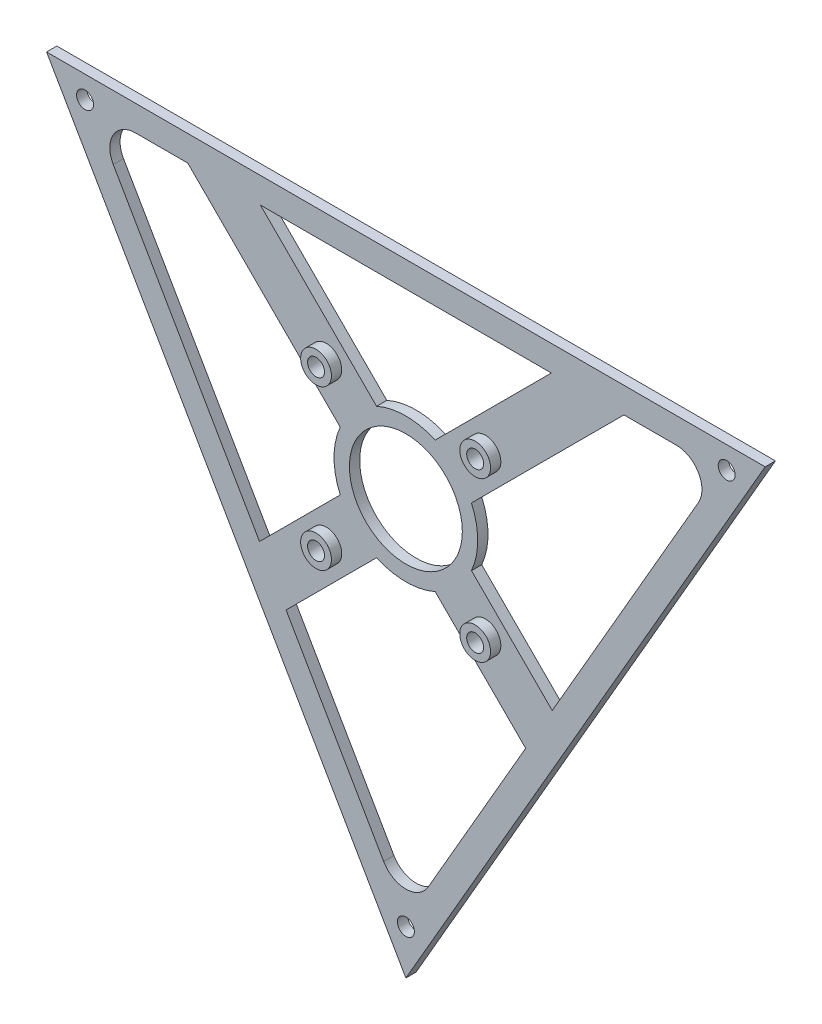
SolidWorks part; units mm, degrees
material "ABS"
ref_plane "Front Plane" through (0, 0, 0) normal (0, 0, 1) x (1, 0, 0)
ref_plane "Top Plane" through (0, 0, 0) normal (0, 1, 0) x (1, 0, 0)
ref_plane "Right Plane" through (0, 0, 0) normal (1, 0, 0) x (0, 0, -1)
sketch "Sketch1" plane through (0, 0, 0) normal (0, 0, 1) x (1, 0, 0)
  line L0 (-15.5, 15.5) -> (15.5, 15.5) construction
  line L5 (0, -80.829) -> (70, 40.4145)
  line L6 (70, 40.4145) -> (-70, 40.4145)
  line L7 (-70, 40.4145) -> (0, -80.829)
  line L8 (15.5, 15.5) -> (15.5, -15.5) construction
  line L9 (15.5, -15.5) -> (-15.5, -15.5) construction
  line L10 (-15.5, -15.5) -> (-15.5, 15.5) construction
  circle A0 centre (0, 0) radius 11
  circle A1 centre (0, 0) radius 40.4145 construction
  circle A2 centre (-15.5, 15.5) radius 1.65
  circle A3 centre (0, 0) radius 11
  circle A4 centre (15.5, 15.5) radius 1.65
  circle A5 centre (0, 0) radius 11
  circle A6 centre (15.5, -15.5) radius 1.65
  circle A7 centre (0, 0) radius 11
  circle A8 centre (-15.5, -15.5) radius 1.65
  point P21 (0, 0)
  dimension "D1" = 22
  dimension "D4" = 3.3
  dimension "D2" = 15.5
  dimension "D3" = 15.5
  dimension "D6" = 140
  dimension "D5" = 4
extrude "Boss-Extrude1" add sketch "Sketch1" along normal blind 2 contours L6 L7 L5 A8 A6 A4 A2 A0 region at (-33.3961, -19.2812, 0)
shell "Shell2" thickness 1 removed face at (-13.85, -15.5, 2)
sketch "Sketch3" plane through (0, 0, 1) normal (0, 0, 1) x (1, 0, 0)
  line L0 (61.3397, 35.4145) -> (-61.3397, 35.4145)
  line L1 (-61.3397, 35.4145) -> (0, -70.829)
  line L2 (0, -70.829) -> (61.3397, 35.4145)
  line L3 (68.2679, 39.4145) -> (-68.2679, 39.4145)
  line L4 (-68.2679, 39.4145) -> (0, -78.829)
  line L5 (0, -78.829) -> (68.2679, 39.4145)
  line L6 (68.2679, 39.4145) -> (-68.2679, 39.4145)
  line L7 (-68.2679, 39.4145) -> (0, -78.829)
  line L8 (0, -78.829) -> (68.2679, 39.4145)
  circle A0 centre (0, 0) radius 12 construction
  circle A1 centre (0, 0) radius 12
  circle A2 centre (-15.5, -15.5) radius 2.65 construction
  circle A3 centre (15.5, -15.5) radius 2.65 construction
  circle A4 centre (15.5, 15.5) radius 2.65 construction
  circle A5 centre (-15.5, 15.5) radius 2.65 construction
  circle A6 centre (-15.5, -15.5) radius 2.65
  circle A7 centre (15.5, -15.5) radius 2.65
  circle A8 centre (15.5, 15.5) radius 2.65
  circle A9 centre (-15.5, 15.5) radius 2.65
  circle A10 centre (-15.5, 15.5) radius 4.65
  circle A11 centre (15.5, 15.5) radius 4.65
  circle A12 centre (0, 0) radius 14
  circle A13 centre (15.5, -15.5) radius 4.65
  circle A14 centre (-15.5, -15.5) radius 4.65
  circle M8 centre (-15.5, -15.5) radius 2.65
  circle M9 centre (15.5, -15.5) radius 2.65
  circle M10 centre (15.5, 15.5) radius 2.65
  circle M11 centre (-15.5, 15.5) radius 2.65
  circle M12 centre (0, 0) radius 12
  line M13 (68.2679, 39.4145) -> (-68.2679, 39.4145)
  line M14 (-68.2679, 39.4145) -> (0, -78.829)
  line M15 (0, -78.829) -> (68.2679, 39.4145)
  dimension "D1" = 0
  dimension "D2" = 4
  dimension "D3" = 2
extrude "Boss-Extrude2" add sketch "Sketch3" along normal up to surface (1 mm away) contours A10 M11 | A11 M10 | A13 M9 | A14 M8 | A12 M12 | L2 L1 L0 M15 M13 M14 region at (32.5698, -18.8042, 1) region at (-20.0185, 15.5, 1) region at (10.9815, 15.5, 1) region at (-13.604, 0, 1) region at (10.9815, -15.5, 1) region at (-20.0185, -15.5, 1) up to face at (-13.85, -15.5, 2)
sketch "Sketch4" plane through (0, 0, 1) normal (0, 0, 1) x (1, 0, 0)
  line L0 (0, 0) -> (25.9252, -25.9252) construction
  line L1 (0, -70.829) -> (61.3397, 35.4145) construction
  line L2 (5.7111, -12.7822) -> (23.337, -30.4081)
  line L3 (28.5134, -21.4423) -> (12.7822, -5.7111)
  line L4 (0, -70.829) -> (61.3397, 35.4145) construction
  line L5 (23.337, -30.4081) -> (28.5134, -21.4423)
  line L6 (0, 0) -> (0, -70.829) construction
  line L7 (-5.7111, -12.7822) -> (-23.337, -30.4081)
  line L8 (-28.5134, -21.4423) -> (-12.7822, -5.7111)
  line L9 (-23.337, -30.4081) -> (-28.5134, -21.4423)
  line L10 (0, 0) -> (-25.9252, -25.9252) construction
  line L11 (0, 0) -> (15.5, 15.5) construction
  line L12 (0, 0) -> (0, 35.4145) construction
  line L13 (61.3397, 35.4145) -> (-61.3397, 35.4145) construction
  line L14 (28.3435, 35.4145) -> (5.7111, 12.7822)
  line L15 (-15.5, 15.5) -> (0, 0) construction
  line L16 (61.3397, 35.4145) -> (-61.3397, 35.4145) construction
  line L17 (42.4856, 35.4145) -> (12.7822, 5.7111)
  line L18 (42.4856, 35.4145) -> (28.3435, 35.4145)
  line L19 (-42.4856, 35.4145) -> (-12.7822, 5.7111)
  line L20 (-28.3435, 35.4145) -> (-5.7111, 12.7822)
  line L21 (-42.4856, 35.4145) -> (-28.3435, 35.4145)
  circle A1 centre (0, 0) radius 14 construction
  circle A2 centre (0, 0) radius 14 construction
  arc A3 (5.7111, -12.7822) -> (12.7822, -5.7111) centre (0, 0) ccw
  circle A4 centre (15.5, -15.5) radius 4.65 construction
  circle A5 centre (15.5, -15.5) radius 4.65
  circle A6 centre (-15.5, -15.5) radius 4.65
  arc A7 (-5.7111, -12.7822) -> (-12.7822, -5.7111) centre (0, 0) cw
  arc A8 (-12.7822, -5.7111) -> (-5.7111, -12.7822) centre (0, 0) ccw
  arc A9 (0, -14) -> (12.7822, -5.7111) centre (0, 0) ccw
  arc A10 (12.7822, 5.7111) -> (5.7111, 12.7822) centre (0, 0) ccw
  circle A11 centre (15.5, 15.5) radius 4.65 construction
  circle A12 centre (15.5, 15.5) radius 4.65
  circle A13 centre (-15.5, 15.5) radius 4.65
  arc A14 (-12.7822, 5.7111) -> (-5.7111, 12.7822) centre (0, 0) cw
  point P7 (15.5, -15.5)
  line M18 (0, -70.829) -> (61.3397, 35.4145)
  line M19 (61.3397, 35.4145) -> (-61.3397, 35.4145)
  line M20 (-61.3397, 35.4145) -> (0, -70.829)
  circle M21 centre (0, 0) radius 14
  circle M22 centre (-15.5, -15.5) radius 4.65
  circle M23 centre (15.5, -15.5) radius 4.65
  circle M24 centre (15.5, 15.5) radius 4.65
  circle M25 centre (-15.5, 15.5) radius 4.65
  dimension "D3" = 5
  dimension "D1" = 5
  dimension "D2" = 5
  dimension "D4" = 5
extrude "Boss-Extrude3" add sketch "Sketch4" along direction (0, 0, 1) on the side of the normal blind 1 contours L8 L7 M20 M21 M22 | L3 L2 M18 M21 M23 | L17 L14 M19 M21 M24 | L20 L19 M19 M21 M25 region at (10.1372, -10.1372, 1) region at (-14.7617, -21.3574, 1) region at (24.4656, 24.0674, 1) region at (-24.4656, 24.0674, 1)
sketch "Sketch6" plane through (0, 0, 1) normal (0, 0, 1) x (1, 0, 0)
  line L0 (-12.7822, 5.7111) -> (-42.4856, 35.4145) construction
  line L1 (-42.4856, 35.4145) -> (-61.3397, 35.4145) construction
  line L2 (-61.3397, 35.4145) -> (-28.5134, -21.4423) construction
  line L3 (-28.5134, -21.4423) -> (-12.7822, -5.7111) construction
  line L4 (0, -70.829) -> (23.337, -30.4081) construction
  line L5 (23.337, -30.4081) -> (5.7111, -12.7822) construction
  line L6 (-5.7111, -12.7822) -> (-23.337, -30.4081) construction
  line L7 (-23.337, -30.4081) -> (0, -70.829) construction
  line L8 (42.4856, 35.4145) -> (12.7822, 5.7111) construction
  line L9 (12.7822, -5.7111) -> (28.5134, -21.4423) construction
  line L10 (28.5134, -21.4423) -> (61.3397, 35.4145) construction
  line L11 (61.3397, 35.4145) -> (42.4856, 35.4145) construction
  line L12 (-28.3435, 35.4145) -> (-5.7111, 12.7822) construction
  line L13 (5.7111, 12.7822) -> (28.3435, 35.4145) construction
  line L14 (28.3435, 35.4145) -> (-28.3435, 35.4145) construction
  line L15 (-12.7822, 5.7111) -> (-42.4856, 35.4145)
  line L16 (-42.4856, 35.4145) -> (-61.3397, 35.4145)
  line L17 (-61.3397, 35.4145) -> (-28.5134, -21.4423)
  line L18 (-28.5134, -21.4423) -> (-12.7822, -5.7111)
  line L19 (0, -70.829) -> (23.337, -30.4081)
  line L20 (23.337, -30.4081) -> (5.7111, -12.7822)
  line L21 (-5.7111, -12.7822) -> (-23.337, -30.4081)
  line L22 (-23.337, -30.4081) -> (0, -70.829)
  line L23 (42.4856, 35.4145) -> (12.7822, 5.7111)
  line L24 (12.7822, -5.7111) -> (28.5134, -21.4423)
  line L25 (28.5134, -21.4423) -> (61.3397, 35.4145)
  line L26 (61.3397, 35.4145) -> (42.4856, 35.4145)
  line L27 (-28.3435, 35.4145) -> (-5.7111, 12.7822)
  line L28 (5.7111, 12.7822) -> (28.3435, 35.4145)
  line L29 (28.3435, 35.4145) -> (-28.3435, 35.4145)
  arc A0 (-12.7822, 5.7111) -> (-12.7822, -5.7111) centre (0, 0) ccw construction
  arc A1 (-5.7111, -12.7822) -> (5.7111, -12.7822) centre (0, 0) ccw construction
  arc A2 (12.7822, -5.7111) -> (12.7822, 5.7111) centre (0, 0) ccw construction
  arc A3 (5.7111, 12.7822) -> (-5.7111, 12.7822) centre (0, 0) ccw construction
  arc A4 (-12.7822, 5.7111) -> (-12.7822, -5.7111) centre (0, 0) ccw
  arc A5 (-5.7111, -12.7822) -> (5.7111, -12.7822) centre (0, 0) ccw
  arc A6 (12.7822, -5.7111) -> (12.7822, 5.7111) centre (0, 0) ccw
  arc A7 (5.7111, 12.7822) -> (-5.7111, 12.7822) centre (0, 0) ccw
extrude "Cut-Extrude2" cut sketch "Sketch6" against normal through all both and the other way through all
fillet "Fillet2" radius 5 3 edges at (0, -70.829, 1) (61.3397, 35.4145, 1) (-61.3397, 35.4145, 1)
sketch "Sketch7" plane through (0, 0, 2) normal (0, 0, 1) x (1, 0, 0)
  line L1 (62.5, 36.0844) -> (-62.5, 36.0844) construction
  line L2 (-62.5, 36.0844) -> (0, -72.1688) construction
  line L3 (0, -72.1688) -> (62.5, 36.0844) construction
  circle A0 centre (-62.5, 36.0844) radius 1.65
  circle A1 centre (62.5, 36.0844) radius 1.65
  circle A2 centre (0, -72.1688) radius 1.65
  circle A3 centre (0, 0) radius 36.0844 construction
  dimension "D1" = 3.3
  dimension "D2" = 125
extrude "Cut-Extrude3" cut sketch "Sketch7" against normal through all
sketch "Sketch8" plane through (0, 0, 2) normal (0, 0, 1) x (1, 0, 0)
  circle A0 centre (-15.5, 15.5) radius 1.65
  circle A1 centre (-15.5, 15.5) radius 3
  circle A2 centre (15.5, 15.5) radius 3
  circle A3 centre (15.5, 15.5) radius 1.65
  circle A4 centre (15.5, -15.5) radius 3
  circle A5 centre (15.5, -15.5) radius 1.65
  circle A6 centre (-15.5, -15.5) radius 3
  circle A7 centre (-15.5, -15.5) radius 1.65
  point P16 (0, 0)
  dimension "D1" = 3.3
  dimension "D2" = 6
  dimension "D3" = 4
extrude "Boss-Extrude4" add sketch "Sketch8" along normal blind 2
